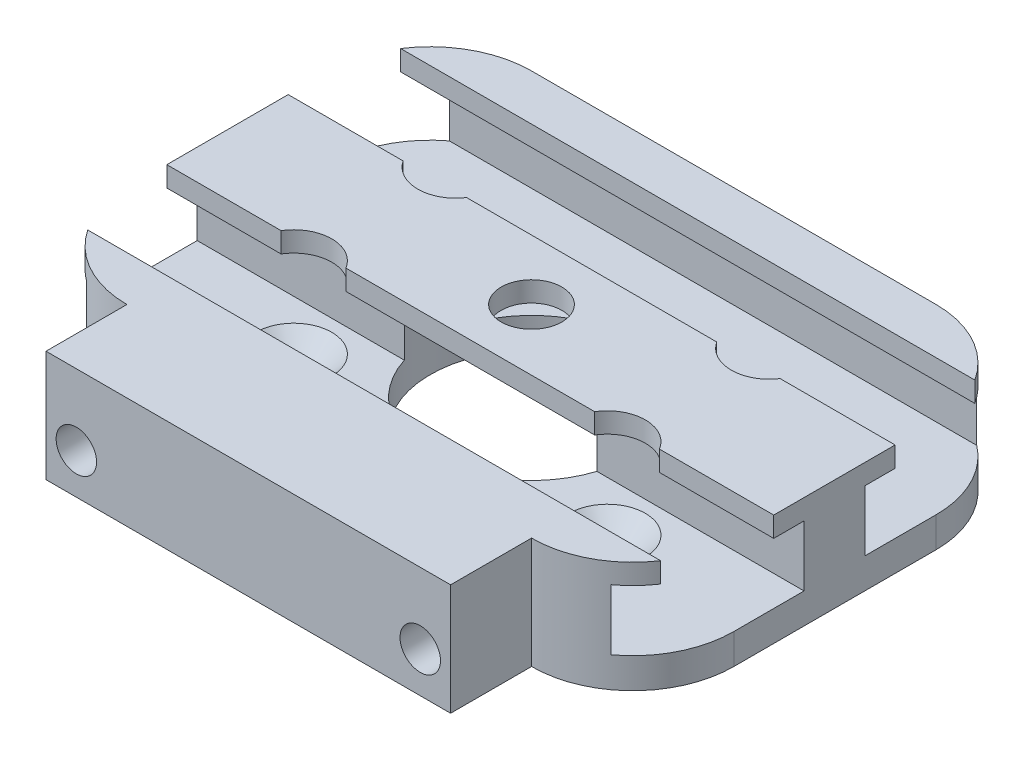
SolidWorks part; units mm, degrees
ref_plane "Front Plane" through (0, 0, 0) normal (0, 0, 1) x (1, 0, 0)
ref_plane "Top Plane" through (0, 0, 0) normal (0, 1, 0) x (1, 0, 0)
ref_plane "Right Plane" through (0, 0, 0) normal (1, 0, 0) x (0, 0, -1)
sketch "Sketch1" plane through (0, 0, 0) normal (0, 1, 0) x (1, 0, 0)
  line L1 (-20, -20) -> (20, -20)
  line L2 (30, -10) -> (30, 10)
  line L3 (20, 20) -> (-20, 20)
  line L4 (-30, 10) -> (-30, -10)
  circle A0 centre (-15.5001, 8.0018) radius 1.7482
  circle A1 centre (-15.5001, -7.9982) radius 1.7482
  circle A2 centre (0, 0) radius 3
  circle A3 centre (0, 0) radius 3
  circle A4 centre (15.5001, -7.9982) radius 1.7482
  circle A5 centre (15.5001, 8.0018) radius 1.7482
  arc A6 (-30, 10) -> (-20, 20) centre (-20, 10) cw
  arc A7 (20, 20) -> (30, 10) centre (20, 10) cw
  arc A8 (-30, -10) -> (-20, -20) centre (-20, -10) ccw
  arc A9 (20, -20) -> (30, -10) centre (20, -10) ccw
  circle A10 centre (0, 0) radius 10
extrude "Boss-Extrude1" add sketch "Sketch1" along normal blind 3 contours L1 A9 L2 A7 L3 A6 L4 A8 A10 A5 A0 A1 A4 region at (-26.5612, 0, 16.5612)
sketch "Sketch2" plane through (30, 0, 0) normal (1, 0, 0) x (0, 0, -1)
  line L0 (-3.0541, 9) -> (-3.0541, 3)
  line L1 (-3.0541, 3) -> (2.9459, 3)
  line L2 (2.9459, 3) -> (2.9459, 9)
  line L3 (5.9459, 9) -> (5.9459, 11)
  line L4 (2.9459, 9) -> (5.9459, 9)
  line L5 (5.9459, 11) -> (-6.0541, 11)
  line L6 (-6.0541, 11) -> (-6.0541, 9)
  line L7 (-6.0541, 9) -> (-3.0541, 9)
  line L8 (-20, 11) -> (-15.5541, 11)
  line L9 (-20, 11) -> (-20, 9)
  line L10 (-20, 9) -> (-15.5541, 9)
  line L11 (-15.5541, 11) -> (-15.5541, 9)
  line L12 (-20, 9) -> (-18.0541, 9)
  line L13 (-20, 9) -> (-20, 3)
  line L14 (-20, 3) -> (-18.0541, 3)
  line L15 (-18.0541, 9) -> (-18.0541, 3)
  line L16 (15.4459, 11) -> (19.9459, 11)
  line L17 (15.4459, 11) -> (15.4459, 9)
  line L18 (15.4459, 9) -> (19.9459, 9)
  line L19 (19.9459, 11) -> (19.9459, 9)
  line L20 (17.9459, 9) -> (19.8729, 9)
  line L21 (17.9459, 9) -> (17.9459, 3)
  line L22 (17.9459, 3) -> (19.8729, 3)
  line L23 (19.8729, 9) -> (19.8729, 3)
  line L24 (-20, 3) -> (-20, 0) construction
  line L25 (-20, 3) -> (-20, 0)
  line L27 (20, 3) -> (19.7378, 3)
  line L28 (20, 3) -> (20, 11)
  line L29 (20, 11) -> (19.7378, 11)
  line L30 (19.7378, 3) -> (19.7378, 11)
  line M3 (10, 3) -> (-10, 3)
extrude "Boss-Extrude2" add sketch "Sketch2" against normal up to surface (60 mm away) contours L6 L7 L0 L2 L4 L3 L5 M3 | L19 L16 L17 L18 | L11 L8 L9 L10 | L15 L10 L13 L14 | L23 L22 L21 L20 region at (30, 7.6, 0.0541) region at (30, 10, 17.777) region at (30, 6, 19.027) region at (30, 10, -17.5919) up to face at (-30, 1.5, 0)
extrude "Boss-Extrude3" add sketch "Sketch2<3>" against normal up to surface (60 mm away) contours L30 L20 L18 L19 L16 | L28 L29 L19 L18 L23 L27 region at (30, 10, -19.8419) region at (30, 6.497, -19.941) up to face at (-30, 5.8333, 0.0361)
sketch "Sketch2<3>" plane through (30, 0, 0) normal (1, 0, 0) x (0, 0, -1) same geometry as "Sketch2"
sketch "Sketch3" plane through (0, 9, 0) normal (0, -1, 0) x (1, 0, 0)
  circle A0 centre (0, 0) radius 10 construction
  circle A1 centre (0, 0) radius 10
extrude "Cut-Extrude1" cut sketch "Sketch3" along normal blind 18
sketch "Sketch4" plane through (0, 0, 0) normal (0, -1, 0) x (1, 0, 0)
  line L1 (-30.6206, 20.4809) -> (33.1723, 20.4809)
  line L2 (-30.6206, 20.4809) -> (-30.6206, -21.2867)
  line L3 (-30.6206, -21.2867) -> (33.1723, -21.2867)
  line L4 (20, 20) -> (-20, 20)
  line L5 (-30, 10) -> (-30, -10)
  line L6 (-20, -20) -> (20, -20)
  line L7 (30, -10) -> (30, 10)
  line L8 (20, 20) -> (-20, 20)
  line L9 (-30, 10) -> (-30, -10)
  line L10 (-20, -20) -> (20, -20)
  line L11 (30, -10) -> (30, 10)
  line L12 (33.1723, 20.4809) -> (33.1723, -21.2867)
  arc A4 (-20, 20) -> (-30, 10) centre (-20, 10) ccw
  arc A5 (-30, -10) -> (-20, -20) centre (-20, -10) ccw
  arc A6 (20, -20) -> (30, -10) centre (20, -10) ccw
  arc A7 (30, 10) -> (20, 20) centre (20, 10) ccw
  arc A8 (-20, 20) -> (-30, 10) centre (-20, 10) ccw
  arc A9 (-30, -10) -> (-20, -20) centre (-20, -10) ccw
  arc A10 (20, -20) -> (30, -10) centre (20, -10) ccw
  arc A11 (30, 10) -> (20, 20) centre (20, 10) ccw
  dimension "D1" = 0
extrude "Cut-Extrude2" cut sketch "Sketch4" against normal blind 29
sketch "Sketch5" plane through (0, 11, 0) normal (0, 1, 0) x (1, 0, 0)
  circle A0 centre (0, 0) radius 3 construction
  circle A1 centre (0, 0) radius 3
extrude "Cut-Extrude3" cut sketch "Sketch5" against normal blind 29
chamfer "Chamfer1" distance 2 1 edges at (-15.5001, 3, 9.7464)
chamfer "Chamfer2" distance 2 angle 45 3 edges at (-15.5001, 3, -6.2536) (15.5001, 3, 9.7464) (15.5001, 3, -6.2536)
sketch "Sketch6" plane through (0, 11, 0) normal (0, 1, 0) x (1, 0, 0)
  circle A0 centre (-15.5001, -7.9982) radius 3.7482 construction
  circle A1 centre (-15.5001, 8.0018) radius 3.7482 construction
  circle A2 centre (15.5001, -7.9982) radius 3.7482 construction
  circle A3 centre (15.5001, 8.0018) radius 3.7482 construction
  circle A4 centre (-15.5001, -7.9982) radius 3.7482
  circle A5 centre (-15.5001, 8.0018) radius 3.7482
  circle A6 centre (15.5001, -7.9982) radius 3.7482
  circle A7 centre (15.5001, 8.0018) radius 3.7482
extrude "Cut-Extrude4" cut sketch "Sketch6" against normal blind 3
sketch "Sketch7" plane through (0, 0, 20) normal (0, 0, 1) x (1, 0, 0)
  line L0 (-19, 0) -> (19, 0)
  line L1 (25, 6) -> (73.5, 6)
  line L2 (73.5, 6) -> (73.5, 11)
  line L3 (73.5, 11) -> (-73.5, 11)
  line L4 (-73.5, 11) -> (-73.5, 6)
  line L5 (-73.5, 6) -> (-25, 6)
  line L6 (0, 11) -> (0, 0)
  line L7 (-20, 11) -> (20, 11) construction
  line L8 (0, 11) -> (0, 0)
  circle A1 centre (-17, 4) radius 1.5
  circle A2 centre (17, 4) radius 1.5
  arc A3 (-22, 3) -> (-25, 6) centre (-25, 3) ccw
  arc A4 (-22, 3) -> (-19, 0) centre (-19, 3) ccw
  arc A5 (19, 0) -> (22, 3) centre (19, 3) ccw
  arc A6 (25, 6) -> (22, 3) centre (25, 3) ccw
extrude "Cut-Extrude5" cut sketch "Sketch7" against normal blind 2 contours A1 | A2 region at (-17, 4, 20) region at (17, 4, 20)
sketch "Sketch9" plane through (0, 11, 0) normal (0, 1, 0) x (1, 0, 0)
  line L5 (-20, -20) -> (20, -20)
  line L6 (-20, -20) -> (-20, -22)
  line L7 (-20, -22) -> (20, -22)
  line L8 (20, -20) -> (20, -22)
extrude "Boss-Extrude4" add sketch "Sketch9" against normal up to vertex (11 mm away) up to point (-20, 0, 20)
sketch "Sketch10" plane through (0, 0, 22) normal (0, 0, 1) x (1, 0, 0)
  line L0 (20, 0) -> (20, 11)
  line L1 (20, 11) -> (-20, 11)
  line L2 (-20, 11) -> (-20, 0)
  line L3 (-20, 0) -> (20, 0)
  line L4 (20, 11) -> (20, 0) construction
  line L5 (20, 11) -> (20, 0)
  circle A0 centre (17, 4) radius 2
  circle A1 centre (-17, 4) radius 2
  line M1 (20, 11) -> (-20, 11)
  line M2 (-20, 11) -> (-20, 0)
  line M3 (-20, 0) -> (20, 0)
  line M4 (20, 0) -> (20, 11)
extrude "Boss-Extrude5" add sketch "Sketch10" along normal blind 6 contours A1 A0 M4 M1 M2 M3 region at (0, 5.5909, 22)
extrude "Cut-Extrude6" cut sketch "Sketch10<3>" against normal up to surface (3.9459 mm away) contours A1 | A0 up to face at (0, 5.125, 18.0541)
sketch "Sketch10<3>" plane through (0, 0, 22) normal (0, 0, 1) x (1, 0, 0) same geometry as "Sketch10"
